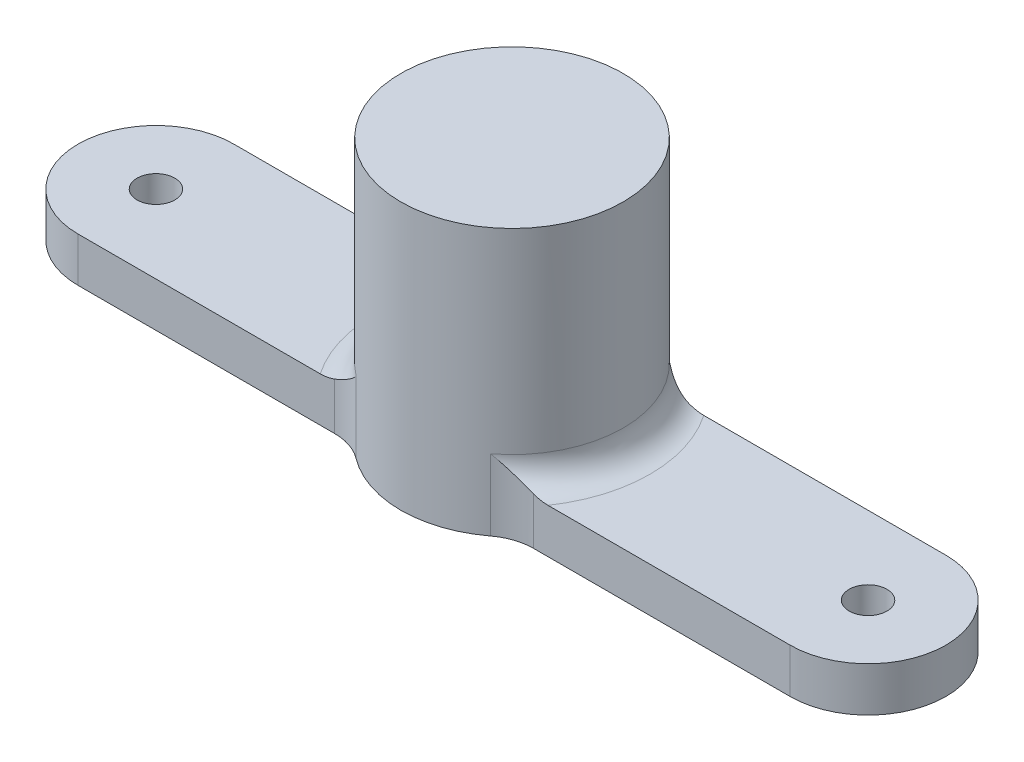
SolidWorks part; units mm, degrees
ref_plane "Front Plane" through (0, 0, 0) normal (0, 0, 1) x (1, 0, 0)
ref_plane "Top Plane" through (0, 0, 0) normal (0, 1, 0) x (1, 0, 0)
ref_plane "Right Plane" through (0, 0, 0) normal (1, 0, 0) x (0, 0, -1)
sketch "Sketch2" plane through (0, 0, 0) normal (0, 1, 0) x (1, 0, 0)
  circle A0 centre (0, 0) radius 12.5
  dimension "D1" = 25
extrude "Boss-Extrude1" add sketch "Sketch2" along normal blind 25
sketch "Sketch3" plane through (0, 0, 0) normal (0, -1, 0) x (1, 0, 0)
  line L0 (-40, 0) -> (40, 0) construction
  line L1 (-40, 8.75) -> (40, 8.75)
  line L2 (-40, -8.75) -> (40, -8.75)
  arc A1 (-40, 8.75) -> (-40, -8.75) centre (-40, 0) ccw
  arc A2 (40, -8.75) -> (40, 8.75) centre (40, 0) ccw
  point P5 (0, 0)
  dimension "D1" = 17.5
  dimension "D2" = 80
extrude "Boss-Extrude2" add sketch "Sketch3" along normal blind 5
sketch "Sketch4" plane through (0, 0, 0) normal (0, -1, 0) x (1, 0, 0)
  line L1 (-8.9268, 8.75) -> (8.9268, 8.75)
  line L2 (-8.9268, 8.75) -> (8.9268, 8.75)
  line L3 (8.9268, -8.75) -> (-8.9268, -8.75)
  line L4 (8.9268, -8.75) -> (-8.9268, -8.75)
  arc A1 (8.9268, 8.75) -> (-8.9268, 8.75) centre (0, 0) ccw
  arc A2 (8.9268, 8.75) -> (-8.9268, 8.75) centre (0, 0) ccw
  arc A3 (-8.9268, -8.75) -> (8.9268, -8.75) centre (0, 0) ccw
  arc A4 (-8.9268, -8.75) -> (8.9268, -8.75) centre (0, 0) ccw
  dimension "D1" = 0
  dimension "D2" = 0
extrude "Boss-Extrude3" add sketch "Sketch4" along normal up to surface (5 mm away) up to face at (0, -5, 0)
fillet "Fillet1" radius 3 2 edges at (12.5, 0, 0) (-12.5, 0, 0)
fillet "Fillet2" radius 6 4 edges at (8.9268, -1, 8.75) (-8.9268, -1, 8.75) (-8.9268, -1, -8.75) (8.9268, -1, -8.75)
sketch "Sketch5" plane through (0, 0, 0) normal (0, 1, 0) x (1, 0, 0)
  line L0 (-48.75, 0) -> (-15.5, 0) construction
  circle A0 centre (-40, 0) radius 2.125
  circle A1 centre (-40, 0) radius 4.15
  arc A2 (-40, 8.75) -> (-40, -8.75) centre (-40, 0) ccw construction
  arc A3 (-12.794, 8.75) -> (-12.794, -8.75) centre (0, 0) ccw construction
  point P12 (-40.6359, 0)
  dimension "D1" = 4.25
  dimension "D2" = 8.3
extrude "Cut-Extrude1" cut sketch "Sketch5" against normal through all contours A0 L0 | L0 A0 region at (-40, 0, 0.9019) region at (-40, 0, -0.9019)
sketch "Sketch6" plane through (0, -5, 0) normal (0, -1, 0) x (1, 0, 0)
  circle A1 centre (-40, 0) radius 4.15
  circle A2 centre (-40, 0) radius 4.15
  circle A3 centre (-40, 0) radius 2.125
  circle A4 centre (-40, 0) radius 2.125
  dimension "D1" = 0
  dimension "D2" = 0
extrude "Cut-Extrude2" cut sketch "Sketch6" against normal blind 2
mirror "Mirror1" about plane through (0, 0, 0) normal (1, 0, 0) of "Cut-Extrude2", "Cut-Extrude1"
